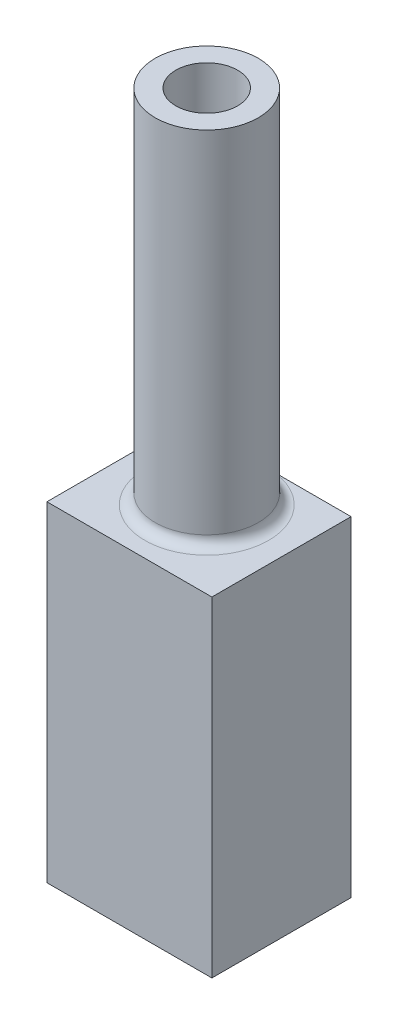
SolidWorks part; units mm, degrees
ref_plane "Front Plane" through (0, 0, 0) normal (0, 0, 1) x (1, 0, 0)
ref_plane "Top Plane" through (0, 0, 0) normal (0, 1, 0) x (1, 0, 0)
ref_plane "Right Plane" through (0, 0, 0) normal (1, 0, 0) x (0, 0, -1)
sketch "Sketch1" plane through (0, 0, 0) normal (0, 0, 1) x (1, 0, 0)
  line L0 (-6, -14) -> (-6, 14)
  line L1 (-8, -16) -> (-4, -16)
  line L2 (-8, -16) -> (-8, 16)
  line L3 (-8, 16) -> (8, 16)
  line L4 (8, -16) -> (8, 16)
  line L5 (-8, -16) -> (8, 16) construction
  line L6 (-8, 16) -> (8, -16) construction
  line L7 (-6, 14) -> (6, 14)
  line L8 (6, -14) -> (6, 14)
  line L9 (-6, -14) -> (-4, -14)
  line L10 (-4, -14) -> (-4, -16)
  line L11 (4, -14) -> (4, -16)
  line L12 (4, -14) -> (6, -14)
  line L13 (-6, -14) -> (6, -14) construction
  line L14 (4, -16) -> (8, -16)
  line L15 (-8, -16) -> (8, -16) construction
  point P0 (0, 0)
  dimension "D1" = 16
  dimension "D2" = 32
  dimension "D4" = 4
  dimension "D5" = 4
  dimension "D3" = 2
extrude "Boss-Extrude1" add sketch "Sketch1" along normal mid plane 12
sketch "Sketch2" plane through (0, 16, 0) normal (0, 1, 0) x (1, 0, 0)
  circle A0 centre (0, 0) radius 5
  dimension "D1" = 10
extrude "Boss-Extrude2" add sketch "Sketch2" along normal blind 35
fillet "Fillet1" radius 1 1 edges at (0, 16, 5)
sketch "Sketch3" plane through (0, 0, 6) normal (0, 0, 1) x (1, 0, 0)
  line L1 (-8, 16) -> (8, 16)
  line L2 (-8, 16) -> (-8, -16)
  line L3 (-8, -16) -> (8, -16)
  line L4 (8, 16) -> (8, -16)
extrude "Boss-Extrude3" add sketch "Sketch3" along normal blind 1.5
sketch "Sketch4" plane through (0, 51, 0) normal (0, 1, 0) x (1, 0, 0)
  circle A0 centre (0, 0) radius 3
  dimension "D1" = 6
extrude "Cut-Extrude1" cut sketch "Sketch4" against normal up to next
